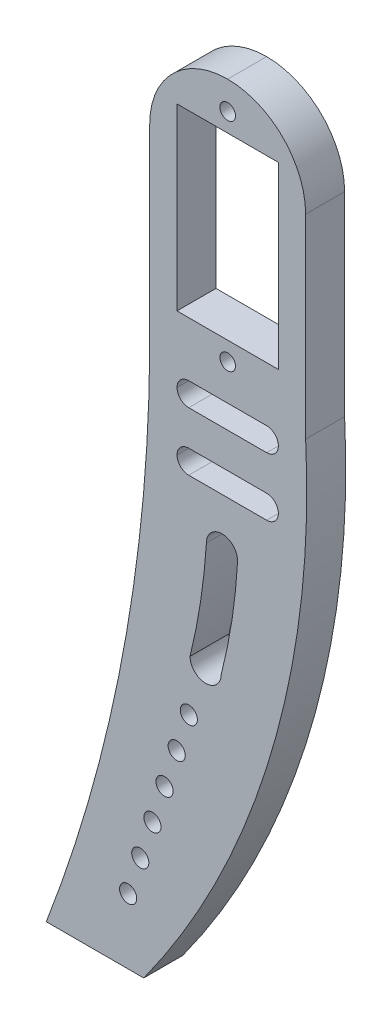
SolidWorks part; units mm, degrees
ref_plane "前视基准面" through (0, 0, 0) normal (0, 0, 1) x (1, 0, 0)
ref_plane "上视基准面" through (0, 0, 0) normal (0, 1, 0) x (1, 0, 0)
ref_plane "右视基准面" through (0, 0, 0) normal (1, 0, 0) x (0, 0, -1)
other "Configuration Table"
sketch "Sketch1" plane through (0, 0, 0) normal (0, 0, 1) x (1, 0, 0)
  line L1 (-6.5, -11.5) -> (6.5, -11.5)
  line L2 (-6.5, -11.5) -> (-6.5, 11.5)
  line L3 (-6.5, 11.5) -> (6.5, 11.5)
  line L4 (6.5, -11.5) -> (6.5, 11.5)
  line L5 (-6.5, -11.5) -> (6.5, 11.5) construction
  line L6 (-6.5, 11.5) -> (6.5, -11.5) construction
  line L7 (-10, -17.5) -> (10, -17.5)
  line L8 (-10, -17.5) -> (-10, 17.5)
  line L9 (-10, 17.5) -> (10, 17.5)
  line L10 (10, -17.5) -> (10, 17.5)
  line L11 (-10, -17.5) -> (10, 17.5) construction
  line L12 (-10, 17.5) -> (10, -17.5) construction
  point P0 (0, 0)
  point P6 (0, 0)
  dimension "D1" = 13
  dimension "D2" = 23
  dimension "D3" = 20
  dimension "D4" = 35
extrude "Boss-Extrude1" add sketch "Sketch1" along normal blind 5
sketch "Sketch2" plane through (0, 0, 5) normal (0, 0, 1) x (1, 0, 0)
  line L0 (0, 0) -> (0, 13.9) construction
  line L1 (0, 0) -> (5.3694, 0) construction
  circle A0 centre (0, 13.9) radius 1
  circle A1 centre (0, -13.9) radius 1
  dimension "D2" = 2
  dimension "D1" = 13.9
extrude "Cut-Extrude1" cut sketch "Sketch2" against normal blind 5
sketch "Sketch4" plane through (0, 0, 5) normal (0, 0, 1) x (1, 0, 0)
  line L0 (-10, -17.5) -> (10, -17.5)
  line L1 (10, -17.5) -> (0, -17.5)
  line L2 (0, -17.5) -> (0, -39.1198) construction
  line L3 (0, -17.5) -> (-34.202, -111.4693) construction
  line L4 (-23.2682, -87.7376) -> (-10.7682, -87.7376)
  arc A1 (10, -17.5) -> (-34.202, -111.4693) centre (-99.8518, -23.2077) cw
  arc A2 (-10, -17.5) -> (-34.202, -111.4693) centre (-209.995, -16.0921) cw
  line M8 (-10, -17.5) -> (10, -17.5)
  dimension "D3" = 110
  dimension "D4" = 200
  dimension "D1" = 20
  dimension "D2" = 100
  dimension "D5" = 12.5
extrude "Boss-Extrude2" add sketch "Sketch4" against normal blind 5 contours A2 A1 L0 M8 region at (-4.6131, -50.3808, 5)
fillet "Fillet1" radius 10 2 edges at (-10, 17.5, 2.5) (10, 17.5, 2.5)
sketch "Sketch6" plane through (0, 0, 5) normal (0, 0, 1) x (1, 0, 0)
  line L0 (-20.2686, -79.3684) -> (-5.2686, -79.3684) construction
  line L1 (-12.7267, -49.0343) -> (7.0733, -49.0343) construction
  line L2 (-10.9267, -35.3736) -> (9.4733, -35.3736) construction
  line L3 (-12.7686, -79.3684) -> (-2.8267, -49.0343) construction
  arc A0 (-23.2682, -87.7376) -> (-10, -17.5) centre (-209.995, -16.0921) ccw construction
  arc A1 (-10.7682, -87.7376) -> (10, -17.5) centre (-99.8518, -23.2077) ccw construction
  circle A2 centre (-12.7686, -79.3684) radius 1.1
  circle A3 centre (-0.7267, -35.3736) radius 2
  circle A4 centre (-2.8267, -49.0343) radius 2
  arc A5 (-2.7267, -35.3736) -> (-4.8267, -49.0343) centre (-80.5679, -30.3991) cw
  arc A6 (1.2733, -35.3736) -> (-0.8267, -49.0343) centre (-68.6259, -31.62) cw
  circle A10 centre (-11.2114, -74.6171) radius 1.1
  circle A11 centre (-9.6542, -69.8658) radius 1.1
  circle A12 centre (-8.0969, -65.1145) radius 1.1
  circle A13 centre (-6.5397, -60.3631) radius 1.1
  circle A14 centre (-4.9824, -55.6118) radius 1.1
  dimension "D4" = 4
  dimension "D5" = 4
  dimension "D6" = 2.2
  dimension "D7" = 78
  dimension "D8" = 70
  dimension "D1" = 15
  dimension "D2" = 20.4
  dimension "D3" = 19.8
  dimension "D9" = 6
  dimension "D10" = 5
extrude "Cut-Extrude2" cut sketch "Sketch6" against normal blind 10 contours A6 A3 A5 A4 | A6 A3 | A4 A5 | A2 | A10 | A11 | A12 | A13 | A14 | A11 region at (-12.7686, -79.3684, 5) region at (-0.7267, -35.3736, 5) region at (-1.4953, -42.2095, 5) region at (-2.8213, -49.0356, 5) region at (-11.2114, -74.6171, 5) region at (-9.6542, -69.8658, 5) region at (-8.0969, -65.1145, 5) region at (-6.5397, -60.3631, 5) region at (-4.9824, -55.6118, 5)
sketch "Sketch7" plane through (0, 0, 5) normal (0, 0, 1) x (1, 0, 0)
  line L0 (0, 0) -> (0, -20) construction
  line L1 (6.5, -29) -> (6.5, -26)
  line L2 (-6.5, -21.5) -> (6.5, -21.5)
  line L3 (-6.5, -21.5) -> (-6.5, -18.5)
  line L4 (-6.5, -18.5) -> (6.5, -18.5)
  line L5 (6.5, -21.5) -> (6.5, -18.5)
  line L6 (-6.5, -21.5) -> (6.5, -18.5) construction
  line L7 (-6.5, -18.5) -> (6.5, -21.5) construction
  line L8 (-6.5, -26) -> (6.5, -26)
  line L9 (-6.5, -29) -> (6.5, -29)
  line L10 (-6.5, -29) -> (-6.5, -26)
  dimension "D1" = 20
  dimension "D2" = 13
  dimension "D3" = 3
  dimension "D4" = 2
extrude "Cut-Extrude3" cut sketch "Sketch7" against normal blind 10
fillet "Fillet2" radius 1.5 8 edges at (6.5, -26, 2.5) (6.5, -29, 2.5) (-6.5, -29, 2.5) (-6.5, -26, 2.5) (6.5, -21.5, 2.5) (6.5, -18.5, 2.5) (-6.5, -21.5, 2.5) (-6.5, -18.5, 2.5)
